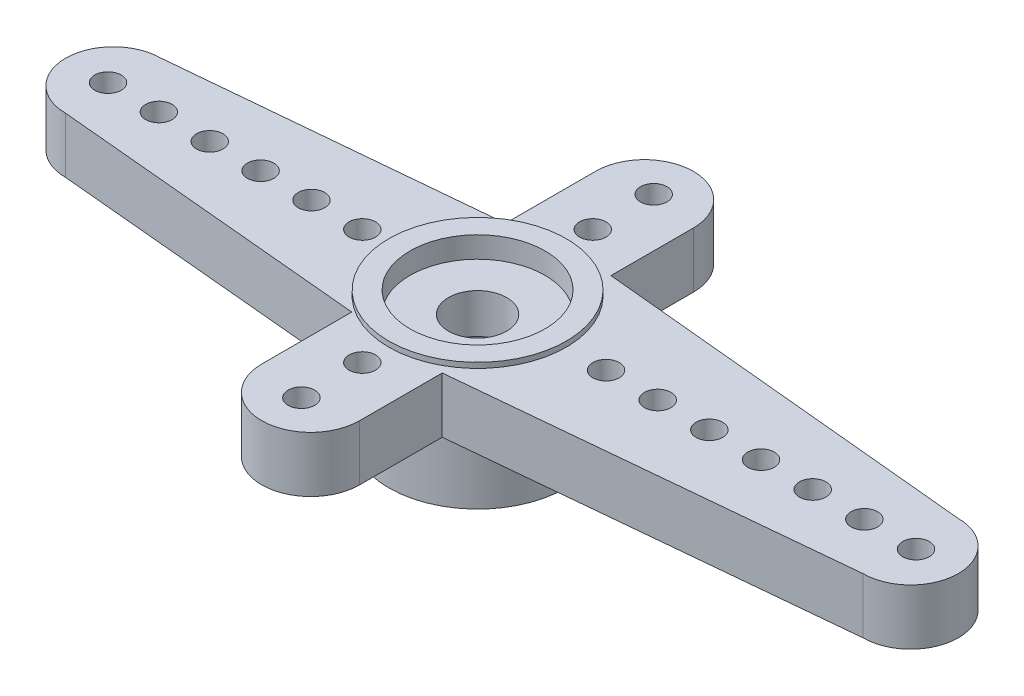
SolidWorks part; units mm, degrees
ref_plane "Plan de face" through (0, 0, 0) normal (0, 0, 1) x (1, 0, 0)
ref_plane "Plan de dessus" through (0, 0, 0) normal (0, 1, 0) x (1, 0, 0)
ref_plane "Plan de droite" through (0, 0, 0) normal (1, 0, 0) x (0, 0, -1)
sketch "Esquisse1" plane through (0, 0, 0) normal (0, 1, 0) x (1, 0, 0)
  line L0 (-7.2643, 3.3473) -> (8.95, 1.8)
  line L1 (-7.2643, -3.3473) -> (8.95, -1.8)
  line L2 (-10.75, 0) -> (10.75, 0) construction
  line L3 (-7.4, 0) -> (-7.4, -3.35) construction
  line L6 (-9.25, -6.3) -> (-5.55, -6.3)
  line L7 (-9.25, 0) -> (-5.55, 0)
  line L8 (-9.25, -6.3) -> (-9.25, 6.3)
  line L9 (-9.25, 6.3) -> (-5.55, 6.3)
  line L10 (-5.55, -6.3) -> (-5.55, 6.3)
  line L11 (-9.25, 2.9) -> (-9.25, -2.9) construction
  line L12 (-9.25, 2.9) -> (-21.15, 1.8)
  line L13 (-21.15, -1.8) -> (-9.25, -2.9)
  arc A0 (-7.2643, 3.3473) -> (-7.5357, 3.3473) centre (-7.4, 0) ccw
  arc A1 (8.95, -1.8) -> (8.95, 1.8) centre (8.95, 0) ccw
  circle A2 centre (-7.4, 0) radius 1.1
  arc A3 (-7.5357, 3.3473) -> (-7.2643, 3.3473) centre (-7.4, 0) cw
  arc A5 (-7.5357, -3.3473) -> (-7.2643, -3.3473) centre (-7.4, 0) ccw
  arc A6 (-7.2643, -3.3473) -> (-7.5357, -3.3473) centre (-7.4, 0) cw
  circle A7 centre (-7.4, 6.3) radius 1.85
  circle A8 centre (-7.4, -6.3) radius 1.85
  circle A9 centre (-21.15, 0) radius 1.8
  point P2 (-7.4, 3.35)
  point P3 (8.95, 1.8)
  point P8 (-10.75, 0)
  point P9 (10.75, 0)
  point P12 (0, 0)
  point P18 (-22.95, 0)
  point P27 (-7.4, 0)
  point P34 (-7.4, 8.15)
  point P35 (-7.4, -8.15)
  point P36 (-9.25, 0)
  point P38 (0, 0)
  dimension "D1" = 6.7
  dimension "D3" = 3.6
  dimension "D4" = 2.2
  dimension "D7" = 16.3
  dimension "D2" = 3.6
  dimension "D5" = 33.7
  dimension "D6" = 3.7
  dimension "D8" = 21.5
  dimension "D9" = 5.451
  dimension "D10" = 5.8
extrude "Boss.-Extru.1" add sketch "Esquisse1" along normal blind 2.1 contours A0 L2 A2 A1 L0 | L2 A0 L1 A1 A2 | L8 | A5 L1 L10 L7 A2 L8 | L8 A8 L10 L1 A5 | A8 L6 | A8 L6 | L9 A7 | L9 A7 | A7 L8 A0 L0 L10 | A9 region at (1.6005, 0, 0) region at (-7.4, 0, -2.6751) region at (-7.4, 0, 2.6751) region at (-7.4, 0, -5.5148) region at (-7.4, 0, -7.0852) region at (-7.4, 0, 7.0852) region at (-7.4, 0, 5.5148) region at (-14.1702, 0, 0)
sketch "Esquisse2" plane through (0, 2.1, 0) normal (0, 1, 0) x (1, 0, 0)
  circle A1 centre (-7.4, 0) radius 1.1 construction
  circle A4 centre (-7.4, 0) radius 3.35
  circle A5 centre (-7.4, 0) radius 2.55
  circle A6 centre (-7.4, 0) radius 1.1
  dimension "D1" = 6.7
  dimension "D2" = 0.8
extrude "Boss.-Extru.2" add sketch "Esquisse2" along normal blind 0.2 contours A4 A5 region at (-10.6552, 2.1, 0)
sketch "Esquisse9" plane through (0, 2.3, 0) normal (0, 1, 0) x (1, 0, 0)
  circle A0 centre (-7.4, 0) radius 2.55 construction
  circle A1 centre (-7.4, 0) radius 2.55
extrude "Enlèv. mat.-Extru.4" cut sketch "Esquisse9" against normal blind 0.8
sketch "Esquisse5" plane through (0, 0, 0) normal (0, -1, 0) x (1, 0, 0)
  circle A6 centre (-7.4, 0) radius 2.55 construction
  circle A15 centre (-7.4, 0) radius 2.55
  circle A16 centre (-7.4, 0) radius 3.35
  dimension "D1" = 6.7
extrude "Boss.-Extru.3" add sketch "Esquisse5" along normal blind 4.8 from surface starting at face at (-7.4, 2.3, 2.55)
sketch "Esquisse7" plane through (0, 2.1, 0) normal (0, 1, 0) x (1, 0, 0)
  line L0 (-7.4, 0) -> (10.75, 0) construction
  line L1 (-7.4, 0) -> (-7.4, -3.35) construction
  line L2 (9.15, 0) -> (10.75, 0) construction
  circle A25 centre (-7.4, 4.35) radius 0.5
  circle A26 centre (-7.4, 6.65) radius 0.5
  arc A31 (8.95, -1.8) -> (8.95, 1.8) centre (8.95, 0) ccw construction
  circle A32 centre (-2.55, 0) radius 0.5
  circle A46 centre (-7.4, 0) radius 3.35 construction
  circle A47 centre (-7.4, 0) radius 3.35
  circle A48 centre (-0.6, 0) radius 0.5
  circle A49 centre (1.35, 0) radius 0.5
  circle A50 centre (3.3, 0) radius 0.5
  circle A51 centre (5.25, 0) radius 0.5
  circle A52 centre (7.2, 0) radius 0.5
  circle A53 centre (9.15, 0) radius 0.5
  arc A61 (-5.55, 6.3) -> (-9.25, 6.3) centre (-7.4, 6.3) ccw construction
  circle A62 centre (-7.4, -6.65) radius 0.5
  circle A63 centre (-7.4, -4.35) radius 0.5
  circle A64 centre (-11.75, 0) radius 0.5
  circle A65 centre (-13.67, 0) radius 0.5
  circle A66 centre (-15.59, 0) radius 0.5
  circle A67 centre (-17.51, 0) radius 0.5
  circle A68 centre (-19.43, 0) radius 0.5
  circle A69 centre (-21.35, 0) radius 0.5
  arc A70 (-21.15, 1.8) -> (-21.15, -1.8) centre (-21.15, 0) ccw construction
  point P3 (9.15, 0)
  point P10 (-4.05, 0)
  point P11 (-7.4, 3.35)
  point P38 (-10.75, 0)
  point P39 (-22.95, 0)
  point P43 (-7.4, 8.15)
  point P52 (-7.4, -8.15)
  dimension "D1" = 1.6
  dimension "D3" = 1
  dimension "D2" = 1
  dimension "D5" = 1.5
  dimension "D4" = 1
  dimension "D6" = 1.5
  dimension "D8" = 1.6
  dimension "D9" = 6
  dimension "D7" = 7
extrude "Enlèv. mat.-Extru.3" cut sketch "Esquisse7" against normal up to next contours A32 | A26 | A25 | A48 | A49 | A50 | A51 | A52 | A53 | A63 | A62 | A69 | A68 | A67 | A66 | A65 | A64
